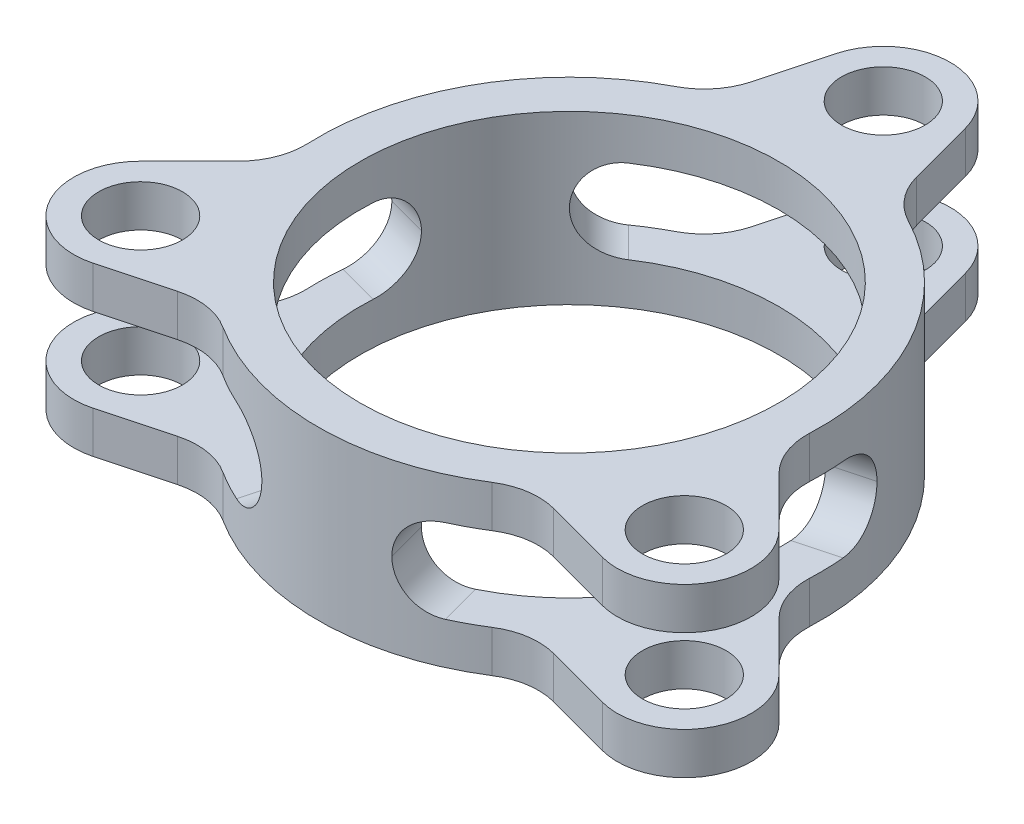
SolidWorks part; units mm, degrees
material "AISI 1020"
ref_plane "Front Plane" through (0, 0, 0) normal (0, 0, 1) x (1, 0, 0)
ref_plane "Top Plane" through (0, 0, 0) normal (0, 1, 0) x (1, 0, 0)
ref_plane "Right Plane" through (0, 0, 0) normal (1, 0, 0) x (0, 0, -1)
sketch "Sketch1" plane through (0, 0, 0) normal (0, 1, 0) x (1, 0, 0)
  line L0 (0, 37.5) -> (0, 0) construction
  line L1 (0, 0) -> (-32.476, -18.75) construction
  line L2 (0, 0) -> (32.476, -18.75) construction
  line L3 (-10.8343, 27.9753) -> (-7.7274, 39.5706)
  line L4 (7.7274, 39.5706) -> (10.8343, 27.9753)
  line L5 (29.6445, -4.6048) -> (38.1328, -13.0931)
  line L6 (30.4054, -26.4774) -> (18.8101, -23.3705)
  line L7 (-18.8101, -23.3705) -> (-30.4054, -26.4774)
  line L8 (-38.1328, -13.0931) -> (-29.6445, -4.6048)
  circle A0 centre (0, 0) radius 25
  circle A1 centre (0, 0) radius 30
  circle A2 centre (0, 0) radius 37.5 construction
  circle A3 centre (0, 37.5) radius 5
  circle A4 centre (-32.476, -18.75) radius 5
  circle A5 centre (32.476, -18.75) radius 5
  arc A7 (-38.1328, -13.0931) -> (-30.4054, -26.4774) centre (-32.476, -18.75) ccw
  arc A8 (30.4054, -26.4774) -> (38.1328, -13.0931) centre (32.476, -18.75) ccw
  arc A9 (7.7274, 39.5706) -> (-7.7274, 39.5706) centre (0, 37.5) ccw
  point P28 (0, 0)
  dimension "D1" = 50
  dimension "D2" = 60
  dimension "D3" = 75
  dimension "D6" = 10
  dimension "D7" = 10
  dimension "D8" = 10
  dimension "D10" = 16
  dimension "D11" = 16
  dimension "D4" = 120
  dimension "D5" = 120
  dimension "D12" = 30
  dimension "D13" = 3
extrude "Boss-Extrude3" add sketch "Sketch1" along normal mid plane 20 contours A1 A0 | L8 A7 L7 A1 A4 | L6 A8 L5 A1 A5 | L4 A9 L3 A1 A3 region at (-9.0117, 0, -33.7008) region at (0, 0, -29.1515) region at (-26.2491, 0, 15.1549) region at (33.6696, 0, 9.0681)
sketch "Sketch2" plane through (0, 0, 0) normal (0, 1, 0) x (1, 0, 0)
  line L0 (0, 45.5) -> (0, 0) construction
  line L1 (0, 0) -> (-39.4042, -22.75) construction
  line L2 (0, 0) -> (39.4042, -22.75) construction
  line L3 (-24.1481, 6.4705) -> (-28.9778, 7.7646)
  line L4 (-6.4705, -24.1481) -> (-7.7646, -28.9778)
  line L5 (6.4705, -24.1481) -> (7.7646, -28.9778)
  line L6 (24.1481, 6.4705) -> (28.9778, 7.7646)
  line L7 (-17.6777, 17.6777) -> (-21.2132, 21.2132)
  line L8 (17.6777, 17.6777) -> (21.2132, 21.2132)
  line L9 (-24.1481, 6.4705) -> (0, 0) construction
  line L10 (-17.6777, 17.6777) -> (0, 0) construction
  line L11 (-6.4705, -24.1481) -> (0, 0) construction
  line L12 (6.4705, -24.1481) -> (0, 0) construction
  line L13 (24.1481, 6.4705) -> (0, 0) construction
  line L14 (17.6777, 17.6777) -> (0, 0) construction
  line L15 (-10.8343, 27.9753) -> (-7.7274, 39.5706) construction
  line L16 (7.7274, 39.5706) -> (10.8343, 27.9753) construction
  line L17 (-10.8343, 27.9753) -> (-7.7274, 39.5706)
  line L18 (7.7274, 39.5706) -> (10.8343, 27.9753)
  line L19 (-18.8101, -23.3705) -> (-30.4054, -26.4774) construction
  line L20 (-38.1328, -13.0931) -> (-29.6445, -4.6048) construction
  line L21 (-18.8101, -23.3705) -> (-30.4054, -26.4774)
  line L22 (-38.1328, -13.0931) -> (-29.6445, -4.6048)
  line L23 (29.6445, -4.6048) -> (38.1328, -13.0931) construction
  line L24 (30.4054, -26.4774) -> (18.8101, -23.3705) construction
  line L25 (29.6445, -4.6048) -> (38.1328, -13.0931)
  line L26 (30.4054, -26.4774) -> (18.8101, -23.3705)
  arc A0 (7.7274, 39.5706) -> (-7.7274, 39.5706) centre (0, 37.5) ccw construction
  arc A1 (-38.1328, -13.0931) -> (-30.4054, -26.4774) centre (-32.476, -18.75) ccw construction
  arc A2 (30.4054, -26.4774) -> (38.1328, -13.0931) centre (32.476, -18.75) ccw construction
  arc A3 (-10.8343, 27.9753) -> (-29.6445, -4.6048) centre (0, 0) ccw construction
  circle A5 centre (0, 0) radius 25 construction
  arc A7 (17.6777, 17.6777) -> (-17.6777, 17.6777) centre (0, 0) ccw
  arc A8 (-18.8101, -23.3705) -> (18.8101, -23.3705) centre (0, 0) ccw construction
  arc A12 (29.6445, -4.6048) -> (10.8343, 27.9753) centre (0, 0) ccw construction
  arc A14 (-10.8343, 27.9753) -> (-21.2132, 21.2132) centre (0, 0) ccw
  arc A15 (-18.8101, -23.3705) -> (-7.7646, -28.9778) centre (0, 0) ccw
  arc A16 (29.6445, -4.6048) -> (28.9778, 7.7646) centre (0, 0) ccw
  arc A17 (21.2132, 21.2132) -> (10.8343, 27.9753) centre (0, 0) ccw
  arc A18 (21.2132, 21.2132) -> (10.8343, 27.9753) centre (0, 0) ccw
  arc A20 (6.4705, -24.1481) -> (24.1481, 6.4705) centre (0, 0) ccw
  arc A21 (-28.9778, 7.7646) -> (-29.6445, -4.6048) centre (0, 0) ccw
  arc A22 (-24.1481, 6.4705) -> (-6.4705, -24.1481) centre (0, 0) ccw
  arc A23 (29.6445, -4.6048) -> (28.9778, 7.7646) centre (0, 0) ccw
  arc A24 (7.7274, 39.5706) -> (-7.7274, 39.5706) centre (0, 37.5) ccw
  arc A25 (29.6445, -4.6048) -> (28.9778, 7.7646) centre (0, 0) ccw
  arc A26 (-38.1328, -13.0931) -> (-30.4054, -26.4774) centre (-32.476, -18.75) ccw construction
  arc A27 (-38.1328, -13.0931) -> (-30.4054, -26.4774) centre (-32.476, -18.75) ccw
  arc A28 (-10.8343, 27.9753) -> (-21.2132, 21.2132) centre (0, 0) ccw
  arc A29 (30.4054, -26.4774) -> (38.1328, -13.0931) centre (32.476, -18.75) ccw construction
  arc A30 (29.6445, -4.6048) -> (28.9778, 7.7646) centre (0, 0) ccw
  arc A31 (30.4054, -26.4774) -> (38.1328, -13.0931) centre (32.476, -18.75) ccw
  arc A32 (-18.8101, -23.3705) -> (-7.7646, -28.9778) centre (0, 0) ccw
  arc A33 (-10.8343, 27.9753) -> (-21.2132, 21.2132) centre (0, 0) ccw
  arc A34 (7.7646, -28.9778) -> (18.8101, -23.3705) centre (0, 0) ccw
  arc A35 (21.2132, 21.2132) -> (10.8343, 27.9753) centre (0, 0) ccw
  arc A36 (-28.9778, 7.7646) -> (-29.6445, -4.6048) centre (0, 0) ccw
  arc A37 (-28.9778, 7.7646) -> (-29.6445, -4.6048) centre (0, 0) ccw
  arc A38 (21.2132, 21.2132) -> (10.8343, 27.9753) centre (0, 0) ccw
  arc A39 (-18.8101, -23.3705) -> (-7.7646, -28.9778) centre (0, 0) ccw
  circle A40 centre (0, 37.5) radius 5 construction
  circle A41 centre (0, 37.5) radius 5
  dimension "D1" = 45
  dimension "D2" = 45
  dimension "D3" = 45
  dimension "D4" = 45
  dimension "D5" = 45
  dimension "D6" = 45
extrude "Cut-Extrude1" cut sketch "Sketch2" against normal blind 5 contours A20 L5 A17 A16 L6 | A22 L3 A17 A15 L4 | L8 A7 L7 A14 A18 region at (-26.8601, 0, 15.5077) region at (26.8601, 0, 15.5077)
extrude "Cut-Extrude2" cut sketch "Sketch2<2>" along normal blind 5 contours L5 A34 L26 A31 L25 A16 L6 A20 | L22 A27 L21 A15 L4 A22 L3 A21 | L18 A24 L17 A14 L7 A7 L8 A17 region at (-26.8601, 0, 15.5077) region at (26.8601, 0, 15.5077) region at (0, 0, -29.7128)
sketch "Sketch2<2>" plane through (0, 0, 0) normal (0, 1, 0) x (1, 0, 0) same geometry as "Sketch2"
sketch "Sketch3" [suppressed] plane through (0, 0, 0) normal (0, 0, 1) x (1, 0, 0)
  line L1 (-7.7646, 5) -> (7.7646, 5) construction
  line L2 (-7.7646, 5) -> (7.7646, 5)
  line L3 (7.7646, -5) -> (-7.7646, -5) construction
  line L4 (7.7646, -5) -> (-7.7646, -5)
  arc A0 (7.7646, -5) -> (7.7646, 5) centre (7.7646, 0) ccw
  arc A1 (-7.7646, 5) -> (-7.7646, -5) centre (-7.7646, 0) ccw
extrude "Cut-Extrude4" cut sketch "Sketch2<4>" against normal blind 5 contours L18 A24 L17 A14 L7 A7 L8 A17 A41 region at (0, 0, -29.7128)
sketch "Sketch2<4>" plane through (0, 0, 0) normal (0, 1, 0) x (1, 0, 0) same geometry as "Sketch2"
fillet "Fillet1" radius 5 1 edges at (-19.4454, 5, -19.4454)
fillet "Fillet2" radius 5 1 edges at (-19.4454, -5, -19.4454)
fillet "Fillet3" radius 5 10 edges at (-7.1175, -5, 26.563) (-7.1175, 5, 26.563) (-26.563, -5, -7.1175) (-26.563, 5, -7.1175) (7.1175, 5, 26.563) (7.1175, -5, 26.563) (26.563, -5, -7.1175) (26.563, 5, -7.1175) (19.4454, -5, -19.4454) (19.4454, 5, -19.4454)
fillet "Fillet4" radius 8 12 edges at (-18.8101, 7.5, 23.3705) (-18.8101, -7.5, 23.3705) (18.8101, -7.5, 23.3705) (18.8101, 7.5, 23.3705) (29.6445, -7.5, 4.6048) (29.6445, 7.5, 4.6048) (10.8343, -7.5, -27.9753) (10.8343, 7.5, -27.9753) (-10.8343, 7.5, -27.9753) (-10.8343, -7.5, -27.9753) (-29.6445, -7.5, 4.6048) (-29.6445, 7.5, 4.6048)
